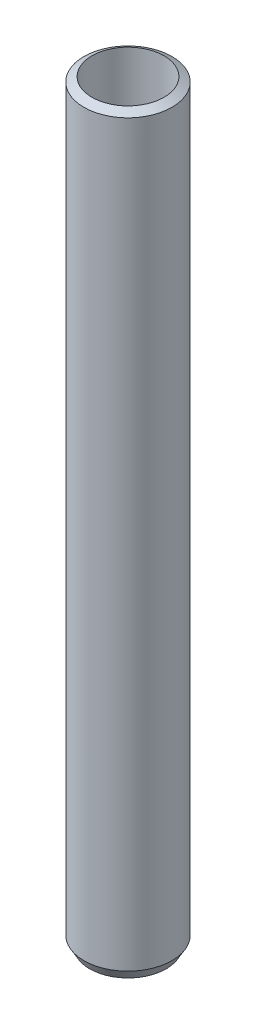
SolidWorks part; units mm, degrees
ref_plane "Front Plane" through (0, 0, 0) normal (0, 0, 1) x (1, 0, 0)
ref_plane "Top Plane" through (0, 0, 0) normal (0, 1, 0) x (1, 0, 0)
ref_plane "Right Plane" through (0, 0, 0) normal (1, 0, 0) x (0, 0, -1)
sketch "Sketch1" plane through (0, 0, 0) normal (0, 1, 0) x (1, 0, 0)
  circle A0 centre (0, 0) radius 35
  dimension "SHAFT_OD" = 70
extrude "Boss-Extrude1" add sketch "Sketch1" along normal blind 600
sketch "Sketch2" plane through (0, 0, 0) normal (0, 1, 0) x (1, 0, 0)
  circle A0 centre (0, 0) radius 28.6271
  dimension "BORE_D" = 57.2543
extrude "Cut-Extrude1" cut sketch "Sketch2" along normal through all
chamfer "Chamfer1" distance 4.5953 angle 60 2 edges at (0, 600, 35) (0, 0, 35) first distance on face at (0, 600, 35) first distance on face at (0, 0, 28.6271)
